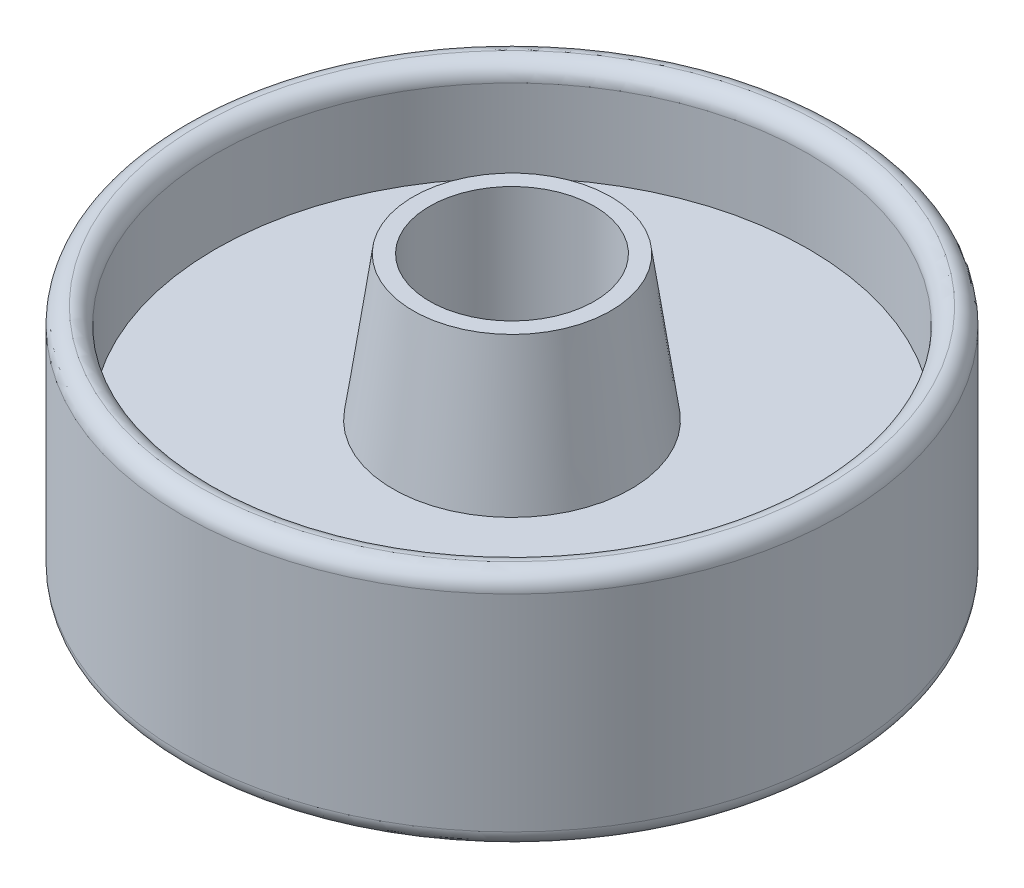
SolidWorks part; units mm, degrees
ref_plane "Front Plane" through (0, 0, 0) normal (0, 0, 1) x (1, 0, 0)
ref_plane "Top Plane" through (0, 0, 0) normal (0, 1, 0) x (1, 0, 0)
ref_plane "Right Plane" through (0, 0, 0) normal (1, 0, 0) x (0, 0, -1)
sketch "Sketch1" plane through (0, 0, 0) normal (0, 0, 1) x (1, 0, 0)
  line L2 (10, -20) -> (12, -20)
  line L3 (10, 20) -> (12, 20)
  line L6 (40, 14.5) -> (36, 14.5)
  line L7 (40, -14.5) -> (36, -14.5)
  line L8 (36, 14.5) -> (36, 2.5)
  line L9 (36, -14.5) -> (36, -2.5)
  line L10 (12, 20) -> (14.4595, 2.5)
  line L11 (12, -20) -> (14.4595, -2.5)
  line L12 (36, -2.5) -> (14.4595, -2.5)
  line L13 (14.4595, 2.5) -> (36, 2.5)
  line L14 (10, 20) -> (10, -20)
  line L15 (40, 14.5) -> (40, -14.5)
  line L16 (0, -24.579) -> (0, 22.7384) construction
  point P0 (11, 20)
  dimension "D1" = 5
  dimension "D2" = 4
  dimension "D3" = 8
  dimension "D4" = 29
  dimension "D5" = 40
  dimension "D6" = 10
  dimension "D7" = 20
  dimension "D8" = 14.5
  dimension "D9" = 36
  dimension "D10" = 36
  dimension "D11" = 2.5
  dimension "D12" = 14.6667
  dimension "D13" = 14.6667
  dimension "D14" = 8
revolve "Revolve1" add sketch "Sketch1" angle 360 about L16
fillet "Fillet2" radius 2 4 edges at (0, 14.5, -36) (0, 14.5, -40) (0, -14.5, -36) (0, -14.5, -40)
